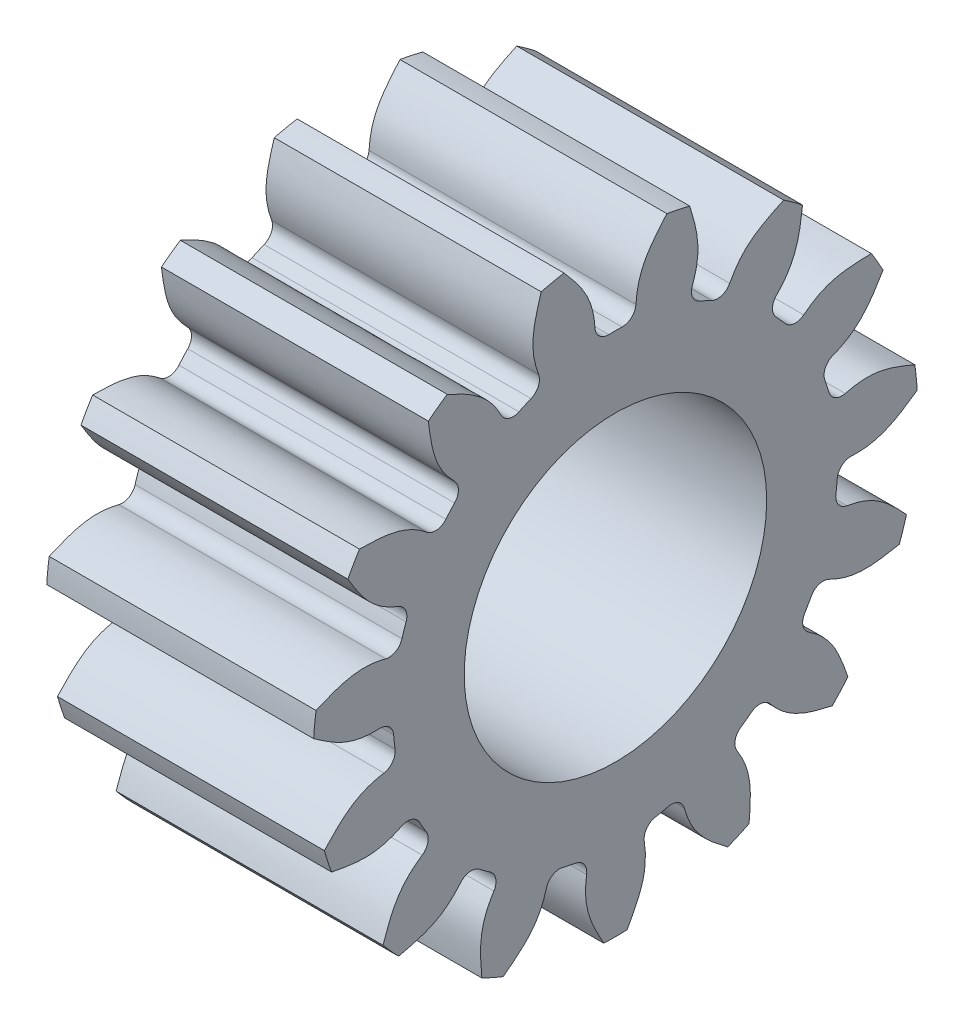
SolidWorks part; units mm, degrees
ref_plane "Plan de face" through (0, 0, 0) normal (0, 0, 1) x (1, 0, 0)
ref_plane "Plan de dessus" through (0, 0, 0) normal (0, 1, 0) x (1, 0, 0)
ref_plane "Plan de droite" through (0, 0, 0) normal (1, 0, 0) x (0, 0, -1)
ref_axis "Axe2" through (-87.4541, 0, 0) along (1, 0, 0)
sketch "Parametre" plane through (0, 0, 0) normal (1, 0, 0) x (0, 0, -1)
  line L0 (-7.2555, 35.3591) -> (-5.2555, 35.3591) construction
  line L1 (-8.3387, 19.1723) -> (6.6613, 19.1723) construction
  line L2 (-7.2555, 11.7492) -> (7.7445, 11.7492) construction
  dimension "D1" = 2
  dimension "D2" = 15
  dimension "D3" = 15
sketch "Esquisse2" plane through (0, 0, 0) normal (1, 0, 0) x (0, 0, -1)
  circle A0 centre (0, 0) radius 17
  dimension "D1" = 34
extrude "Extrusion1" add sketch "Esquisse2" against normal blind 15
sketch "Esquisse4" plane through (0, 0, 0) normal (1, 0, 0) x (0, 0, -1)
  line L0 (0, 0) -> (0, 35.1994) construction
  line L1 (0, 0) -> (-1.777, 16.9069) construction
  line L2 (0, 0) -> (1.777, 16.9069) construction
  line L3 (-1.5679, 14.9178) -> (-2.6437, 17.1235) construction
  line L4 (-1.5679, 14.9178) -> (-6.179, 12.6689) construction
  line L5 (-6.179, 12.6689) -> (0, 0) construction
  line L6 (0, 0) -> (-14.0954, 0) construction
  line L7 (-9.752, 10.1774) -> (-2.89, 16.7526) construction
  line L8 (0, 0) -> (12.7636, 16.5183) construction
  line L9 (-1.2643, 14.0386) -> (-1.1212, 12.4496) construction
  line L10 (-1.2643, 14.0386) -> (-2.3074, 13.9446) construction
  arc A0 (1.5679, 14.9178) -> (-1.5679, 14.9178) centre (0, 0) ccw construction
  arc A1 (1.3066, 12.4315) -> (-1.3066, 12.4315) centre (0, 0) ccw construction
  circle A2 centre (0, 0) radius 17 construction
  arc A3 (-6.179, 12.6689) -> (-14.0954, 0) centre (0, 0) ccw construction
  point P16 (-1.2643, 14.0386)
  point P18 (1.2643, 14.0386)
  point P19 (2.89, 16.7526)
  point P23 (1.1212, 12.4496)
  dimension "D1" = 30
  dimension "D2" = 25
  dimension "D3" = 20
  dimension "D4" = 12
  dimension "D5" = 15.7447
  dimension "D6" = 5.1303
  dimension "D7" = 20.875
  dimension "D8" = 9.5037
  dimension "D9" = 11.3713
  dimension "D10" = 20.875
sketch "Esquisse6" plane through (0, 0, 0) normal (1, 0, 0) x (0, 0, -1)
  line L0 (0, 0) -> (0, 35.1994) construction
  line L1 (0, 0) -> (0, 35.1994) construction
  arc A0 (1.3066, 12.4315) -> (-1.3066, 12.4315) centre (0, 0) ccw construction
  arc A1 (1.1212, 12.4496) -> (-1.1212, 12.4496) centre (0, 0) ccw
  circle A2 centre (0, 0) radius 17 construction
  arc A3 (2.89, 16.7526) -> (-2.89, 16.7526) centre (0, 0) ccw
  spline S0 degree 3 poles (-2.89, 16.7526) (-2.3904, 16.1752) (-1.6853, 15.3603) (-1.1556, 13.8317) (-1.1345, 12.9847) (-1.1212, 12.4496) knots 0 0 0 0 0.472407 0.666726 1 1 1 1
  spline S1 degree 3 poles (2.89, 16.7526) (2.3904, 16.1752) (1.6853, 15.3603) (1.1556, 13.8317) (1.1345, 12.9847) (1.1212, 12.4496) knots 0 0 0 0 0.472407 0.666726 1 1 1 1
extrude "Extrusion2" cut sketch "Esquisse6" against normal through all
fillet "Congé1" radius 0.76 2 edges at (-7.5, 12.4496, -1.1212) (-7.5, 12.4496, 1.1212)
pattern_circular "Répétition circulaire1" count 15 over 360 about axis through (-15, 0, 0) along (1, 0, 0) of "Extrusion2", "Congé1"
sketch "Esquisse7" plane through (0, 0, 0) normal (1, 0, 0) x (0, 0, -1)
  circle A0 centre (0, 0) radius 8.5
  dimension "D1" = 17
extrude "Extrusion3" cut sketch "Esquisse7" against normal through all
equation "\"D1@Esquisse2\" = \"D1@Parametre\"*\"D2@Parametre\"+2*\"D1@Parametre\""
equation "\"D1@Extrusion1\" = \"D3@Parametre\""
equation "\"D1@Esquisse4\" = \"D1@Parametre\"*\"D2@Parametre\""
equation "\"D2@Esquisse4\" = \"D1@Esquisse4\"-2*1.25*\"D1@Parametre\""
equation "\"D4@Esquisse4\" = 360/\"D2@Parametre\"/2"
equation "\"D7@Esquisse4\" = \"D6@Esquisse4\"+\"D5@Esquisse4\""
equation "\"D9@Esquisse4\" = \"D7@Esquisse4\"-\"D8@Esquisse4\""
equation "\"D10@Esquisse4\" = \"D7@Esquisse4\""
equation "\"D1@Congé1\" = 0.38*\"D1@Parametre\""
equation "\"D1@Répétition circulaire1\" = \"D2@Parametre\""
